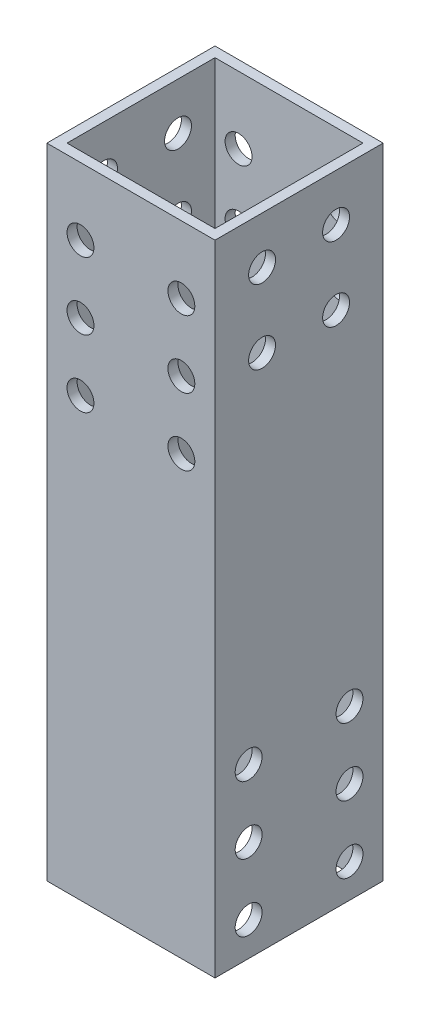
SolidWorks part; units mm, degrees
material "1060 Alloy"
ref_plane "Front Plane" through (0, 0, 0) normal (0, 0, 1) x (1, 0, 0)
ref_plane "Top Plane" through (0, 0, 0) normal (0, 1, 0) x (1, 0, 0)
ref_plane "Right Plane" through (0, 0, 0) normal (1, 0, 0) x (0, 0, -1)
sketch "Sketch3" plane through (0, 0, 0) normal (0, 1, 0) x (1, 0, 0)
  line L0 (0, 86.7063) -> (0, -87.1032) construction
  line L1 (-136.9048, 0) -> (130.9524, 0) construction
  line L7 (-12.5, 12.5) -> (12.5, 12.5)
  line L8 (-12.5, 12.5) -> (-12.5, -12.5)
  line L13 (-12.5, -12.5) -> (12.5, -12.5)
  line L14 (12.5, 12.5) -> (12.5, -12.5)
  line L15 (-12.5, 12.5) -> (12.5, -12.5) construction
  line L16 (-12.5, -12.5) -> (12.5, 12.5) construction
  line L17 (-11, 11) -> (11, 11)
  line L18 (-11, 11) -> (-11, -11)
  line L19 (-11, -11) -> (11, -11)
  line L20 (11, 11) -> (11, -11)
  line L21 (-11, 11) -> (11, -11) construction
  line L22 (-11, -11) -> (11, 11) construction
  point P5 (0, 0)
  point P10 (0, 0)
  dimension "D1" = 25
  dimension "D2" = 25
  dimension "D3" = 22
extrude "Boss-Extrude1" add sketch "Sketch3" along normal blind 47.5 and the other way blind 47.5
sketch "Sketch6" plane through (12.5, 0, 0) normal (1, 0, 0) x (0, 0, -1)
  line L0 (0, 0) -> (0, -102.9817) construction
  line L1 (-12.5, -47.5) -> (12.5, -47.5) construction
  circle A0 centre (7.5, -42.5) radius 2
  circle A1 centre (7.5, -22.5) radius 2
  circle A3 centre (-7.5, -42.5) radius 2
  circle A4 centre (-7.5, -22.5) radius 2
  circle A5 centre (7.5, -32.5) radius 2
  circle A6 centre (-7.5, -32.5) radius 2
  dimension "D2" = 10
  dimension "D9" = 10
  dimension "D3" = 7.5
  dimension "D4" = 7.5
  dimension "D5" = 7.5
  dimension "D6" = 7.5
  dimension "D7" = 5
  dimension "D8" = 10
  dimension "D10" = 5
  dimension "D11" = 10
  dimension "D12" = 7.5
  dimension "D13" = 7.5
extrude "Cut-Extrude3" cut sketch "Sketch6" against normal blind 25
sketch "Sketch7" plane through (0, 0, -12.5) normal (0, 0, -1) x (-1, 0, 0)
  line L0 (0, 0) -> (0, 70.1061) construction
  line L2 (-12.5, 47.5) -> (12.5, 47.5) construction
  circle A0 centre (7.5, 37.5) radius 2
  circle A1 centre (7.5, 27.5) radius 2
  circle A3 centre (-7.5, 37.5) radius 2
  circle A4 centre (-7.5, 27.5) radius 2
  circle A5 centre (-7.5, 17.5) radius 2
  circle A6 centre (7.5, 17.5) radius 2
  dimension "D1" = 7.5
  dimension "D5" = 10
  dimension "D2" = 7.5
  dimension "D3" = 7.5
  dimension "D4" = 7.5
  dimension "D6" = 10
  dimension "D7" = 10
  dimension "D8" = 10
  dimension "D9" = 7.5
  dimension "D10" = 10
  dimension "D11" = 7.5
  dimension "D12" = 10
extrude "Cut-Extrude4" cut sketch "Sketch7" against normal blind 25
sketch "Sketch8" plane through (12.5, 0, 0) normal (1, 0, 0) x (0, 0, -1)
  line L0 (12.5, -47.5) -> (12.5, 47.5) construction
  line L1 (-12.5, -47.5) -> (-12.5, 47.5) construction
  line L2 (-12.5, 47.5) -> (12.5, 47.5) construction
  circle A0 centre (5.5, 40.5) radius 2
  circle A1 centre (5.5, 29.5) radius 2
  circle A2 centre (-5.5, 29.5) radius 2
  circle A3 centre (-5.5, 40.5) radius 2
  dimension "D1" = 7
  dimension "D2" = 7
  dimension "D3" = 7
  dimension "D4" = 7
  dimension "D5" = 11
  dimension "D6" = 11
  dimension "D7" = 7
  dimension "D8" = 7
extrude "Cut-Extrude5" cut sketch "Sketch8" against normal blind 25
